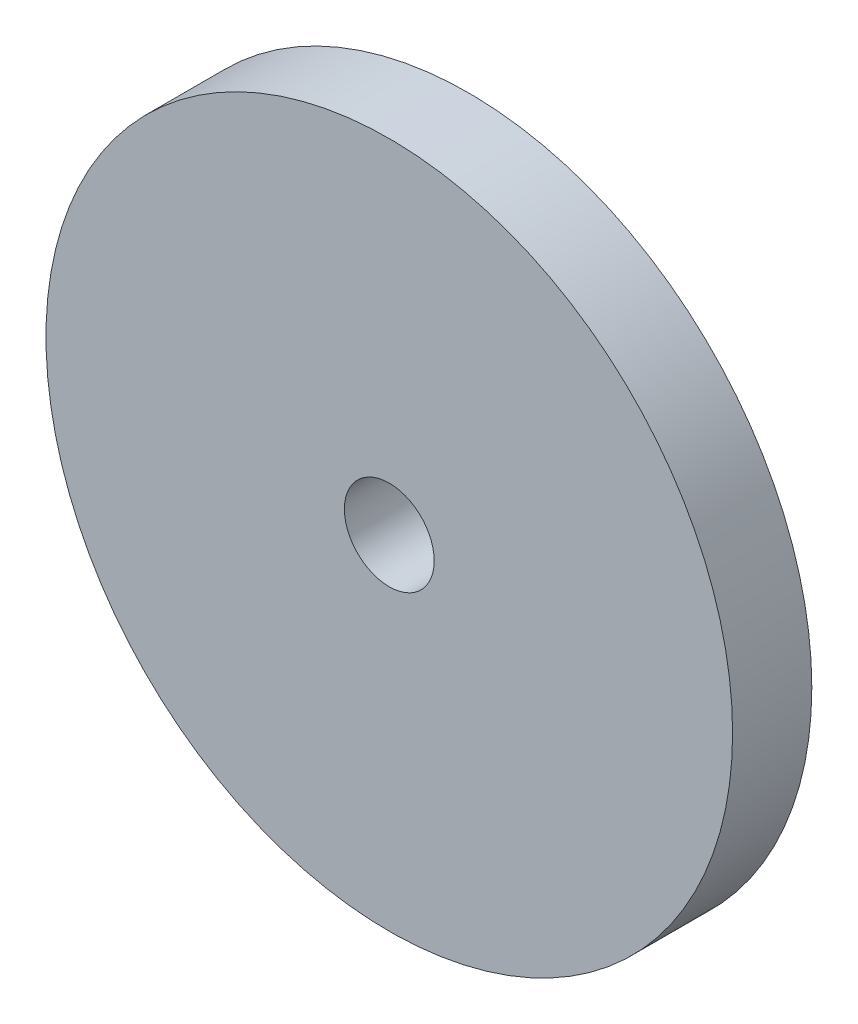
SolidWorks part; units mm, degrees
material "Custom Plastic"
ref_plane "Front Plane" through (0, 0, 0) normal (0, 0, 1) x (1, 0, 0)
ref_plane "Top Plane" through (0, 0, 0) normal (0, 1, 0) x (1, 0, 0)
ref_plane "Right Plane" through (0, 0, 0) normal (1, 0, 0) x (0, 0, -1)
sketch "Sketch1" plane through (0, 0, 0) normal (0, 0, 1) x (1, 0, 0)
  circle A2 centre (-132.5, 0) radius 1.7
  circle A3 centre (-132.5, 0) radius 13
extrude "Boss-Extrude1" add sketch "Sketch1" along normal blind 3
sketch "Sketch2" plane through (0, 0, 0) normal (0, 0, -1) x (-1, 0, 0)
  circle A0 centre (132.5, 0) radius 4 construction
  circle A1 centre (132.5, 0) radius 4
  circle A2 centre (132.5, 0) radius 1.7 construction
  circle A3 centre (132.5, 0) radius 1.7
extrude "Boss-Extrude2" add sketch "Sketch2" along normal blind 5 contours A1 | A3
chamfer "Chamfer1" distance 5 distance2 1 1 edges at (-136.5, 0, -5) first distance on face at (-136.5, 0, -5)
